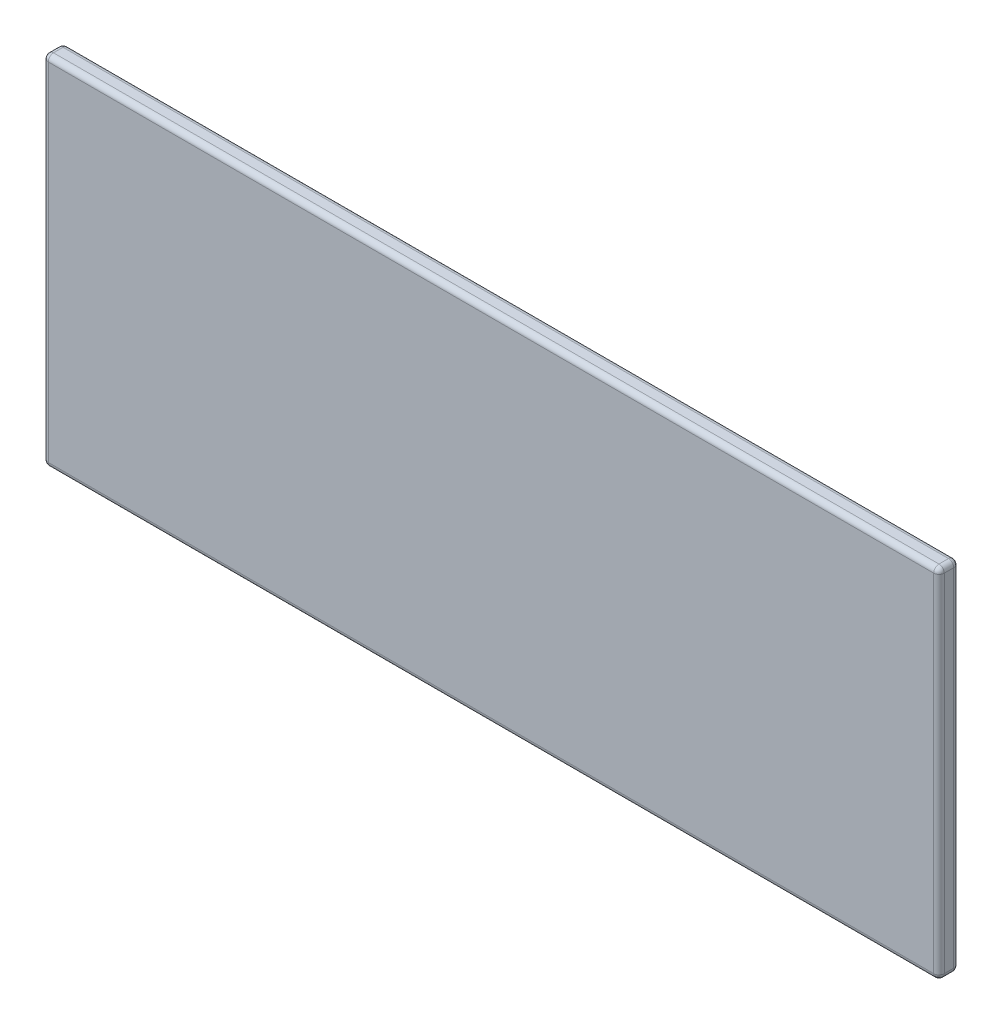
SolidWorks part; units mm, degrees
ref_plane "前视基准面" through (0, 0, 0) normal (0, 0, 1) x (1, 0, 0)
ref_plane "上视基准面" through (0, 0, 0) normal (0, 1, 0) x (1, 0, 0)
ref_plane "右视基准面" through (0, 0, 0) normal (1, 0, 0) x (0, 0, -1)
other "Configuration Table"
sketch "草图1" plane through (0, 0, 0) normal (0, 0, 1) x (1, 0, 0)
  line L1 (85, -33.9) -> (-85, -33.9)
  line L2 (85, -33.9) -> (85, 33.9)
  line L3 (85, 33.9) -> (-85, 33.9)
  line L4 (-85, -33.9) -> (-85, 33.9)
  line L5 (85, -33.9) -> (-85, 33.9) construction
  line L6 (85, 33.9) -> (-85, -33.9) construction
  point P0 (0, 0)
  dimension "D1" = 170
  dimension "D2" = 67.8
extrude "凸台-拉伸1" add sketch "草图1" along normal blind 3.8
fillet "圆角1" radius 1 12 edges at (0, -33.9, 3.8) (0, -33.9, 0) (0, 33.9, 3.8) (0, 33.9, 0) (-85, 33.9, 1.9) (-85, 0, 3.8) (-85, -33.9, 1.9) (-85, 0, 0) (85, -33.9, 1.9) (85, 0, 3.8) (85, 33.9, 1.9) (85, 0, 0)
